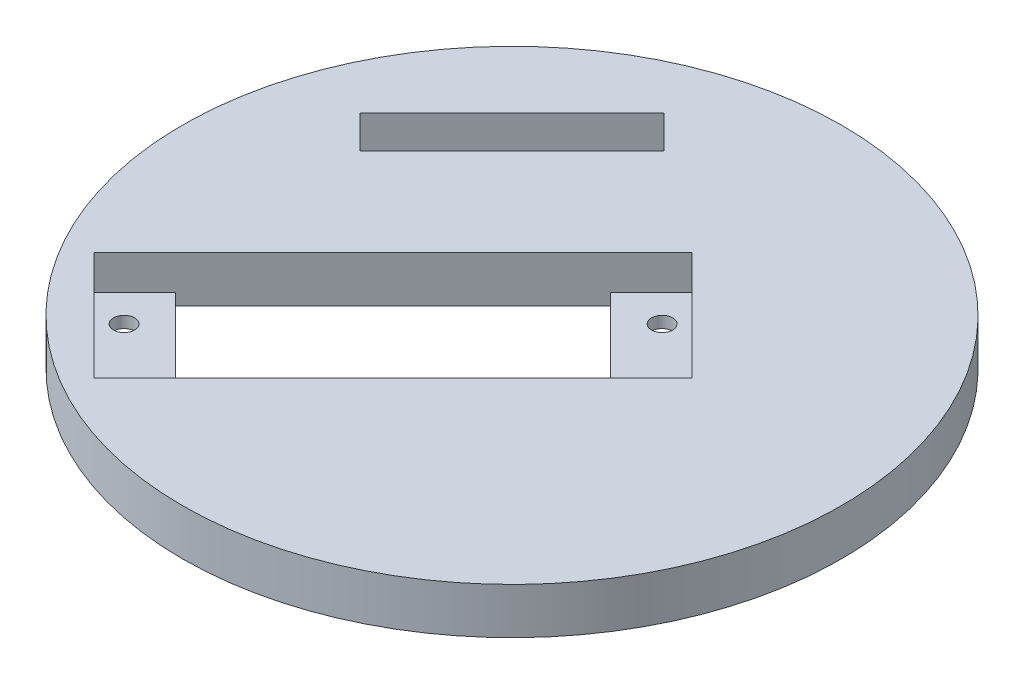
SolidWorks part; units mm, degrees
ref_plane "Front Plane" through (0, 0, 0) normal (0, 0, 1) x (1, 0, 0)
ref_plane "Top Plane" through (0, 0, 0) normal (0, 1, 0) x (1, 0, 0)
ref_plane "Right Plane" through (0, 0, 0) normal (1, 0, 0) x (0, 0, -1)
sketch "Sketch1" plane through (0, 0, 0) normal (0, 1, 0) x (1, 0, 0)
  line L11 (4.6392, 18.7813) -> (18.7813, 4.6392)
  line L12 (18.7813, 4.6392) -> (-20.1096, -34.2517)
  line L17 (-20.1096, -34.2517) -> (-34.2517, -20.1096)
  line L18 (-34.2517, -20.1096) -> (4.6392, 18.7813)
  line L22 (-0.6641, 13.478) -> (13.478, -0.6641)
  line L23 (13.478, -0.6641) -> (-14.8063, -28.9484)
  line L24 (-14.8063, -28.9484) -> (-28.9484, -14.8063)
  circle A0 centre (0, 0) radius 3.4217
  circle A1 centre (0, 0) radius 42.8758
  point P15 (-0.6641, -14.8063)
  point P16 (-0.6641, -14.8063)
  dimension "D2" = 20
  dimension "D3" = 55
  dimension "D4" = 40
  dimension "D5" = 16.5608
extrude "Boss-Extrude1" add sketch "Sketch1" along normal blind 6 contours A1 L17 L18 L11 L12 region at (-41.6631, 0, 0)
extrude "Boss-Extrude2" add sketch "Sketch1<4>" along normal blind 1.5 contours L18 L22 L12 L11 | L12 L24 L18 L17 region at (9.0586, 0, -9.0586) region at (-24.529, 0, 24.529)
sketch "Sketch1<4>" plane through (0, 0, 0) normal (0, 1, 0) x (1, 0, 0) same geometry as "Sketch1"
sketch "Sketch2" plane through (0, 6, 0) normal (0, 1, 0) x (1, 0, 0)
  line L0 (-32.6765, 12.8775) -> (-12.8775, 32.6765)
  line L1 (-12.8775, 32.6765) -> (-8.6348, 28.4338)
  line L2 (-8.6348, 28.4338) -> (-28.4338, 8.6348)
  line L3 (-28.4338, 8.6348) -> (-32.6765, 12.8775)
  line L5 (-30.3178, 30.3178) -> (30.3178, -30.3178) construction
  line L6 (-34.2517, -20.1096) -> (4.6392, 18.7813) construction
  circle A0 centre (0, 0) radius 42.8758 construction
  point P2 (0, 0)
  point P9 (-18.5343, 18.5343)
  dimension "D1" = 6
  dimension "D2" = 28
extrude "Cut-Extrude1" cut sketch "Sketch2" against normal up to next
sketch "Sketch3" plane through (0, 0, 0) normal (0, -1, 0) x (1, 0, 0)
  line L0 (-38.8758, -2.5) -> (-38.8758, 2.5) construction
  line L3 (-39.6258, -2.5) -> (-39.6258, 2.5)
  line L4 (-38.1258, -2.5) -> (-38.1258, 2.5)
  line L5 (-37.8758, 2.5) -> (-37.8758, -2.5) construction
  line L6 (42.8758, 0) -> (-42.8758, 0) construction
  circle A2 centre (0, 0) radius 42.8758 construction
  arc A3 (-39.6258, -2.5) -> (-38.1258, -2.5) centre (-38.8758, -2.5) ccw
  arc A4 (-38.1258, 2.5) -> (-39.6258, 2.5) centre (-38.8758, 2.5) ccw
  point P2 (-38.8758, 0)
  dimension "D1" = 0.25
extrude "Cut-Extrude2" cut sketch "Sketch3" against normal offset from surface (4 mm away) 2 up to face at (-20.6556, 6, -20.6556)
ref_axis "Axis1" through (0, 0, 0) along (0, -1, 0)
pattern_circular "CirPattern1" count 4 over 360 about axis through (0, 0, 0) along (0, -1, 0) of "Cut-Extrude2"
sketch "Sketch4" plane through (0, 0, 0) normal (0, -1, 0) x (1, 0, 0)
  line L4 (-12.7368, 29.6062) -> (31.8109, -14.9415)
  line L5 (31.8109, -14.9415) -> (50.9028, 4.1504)
  line L6 (50.9028, 4.1504) -> (6.3551, 48.6981)
  line L7 (6.3551, 48.6981) -> (-12.7368, 29.6062)
  line L12 (13.478, 0.6641) -> (-14.8063, 28.9484) construction
  dimension "D3" = 27
  dimension "D4" = 63
sketch "Sketch5" plane through (0, 1.5, 0) normal (0, 1, 0) x (1, 0, 0)
  circle A0 centre (13.3012, 6.2302) radius 1.375
  circle A1 centre (6.2302, 13.3012) radius 1.375
  dimension "D1" = 2.75
  dimension "D2" = 2.75
extrude "Cut-Extrude3" cut sketch "Sketch5" against normal up to next
ref_plane "Plane1" through (-7.7352, 0, 7.7352) normal (-0.7071, 0, 0.7071) x (0.7071, 0, 0.7071)
mirror "Mirror1" about plane through (-7.7352, 0, 7.7352) normal (-0.7071, 0, 0.7071) of "Cut-Extrude3"
equation "\"D2@Sketch5\"=\"D1@Sketch5\""
